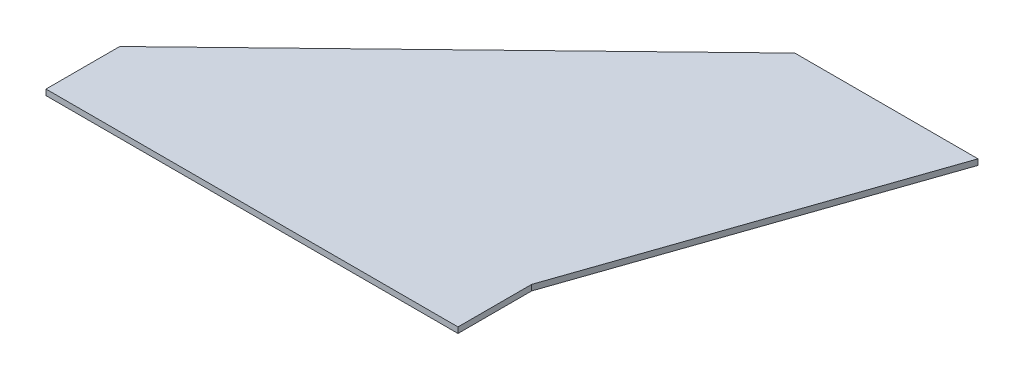
SolidWorks part; units mm, degrees
ref_plane "Front Plane" through (0, 0, 0) normal (0, 0, 1) x (1, 0, 0)
ref_plane "Top Plane" through (0, 0, 0) normal (0, 1, 0) x (1, 0, 0)
ref_plane "Right Plane" through (0, 0, 0) normal (1, 0, 0) x (0, 0, -1)
sketch "Sketch1" plane through (0, 0, 0) normal (0, 1, 0) x (1, 0, 0)
  line L0 (0, 40.894) -> (190.5, 225.044)
  line L1 (0, 0) -> (228.6, 0)
  line L2 (0, 0) -> (0, 40.894)
  line L3 (0, 40.894) -> (228.6, 40.894)
  line L4 (228.6, 0) -> (228.6, 40.894)
  line L5 (190.5, 225.044) -> (292.1, 225.044)
  line L6 (292.1, 225.044) -> (228.6, 40.894)
  dimension "D1" = 228.6
  dimension "D2" = 190.5
  dimension "D3" = 184.15
  dimension "D4" = 101.6
  dimension "D5" = 40.894
extrude "Boss-Extrude1" add sketch "Sketch1" along normal blind 3.175 contours L1 L4 L3 L2 | L6 L5 L0 L3 region at (114.3, 0, -20.447) region at (169.659, 0, -121.1645)
